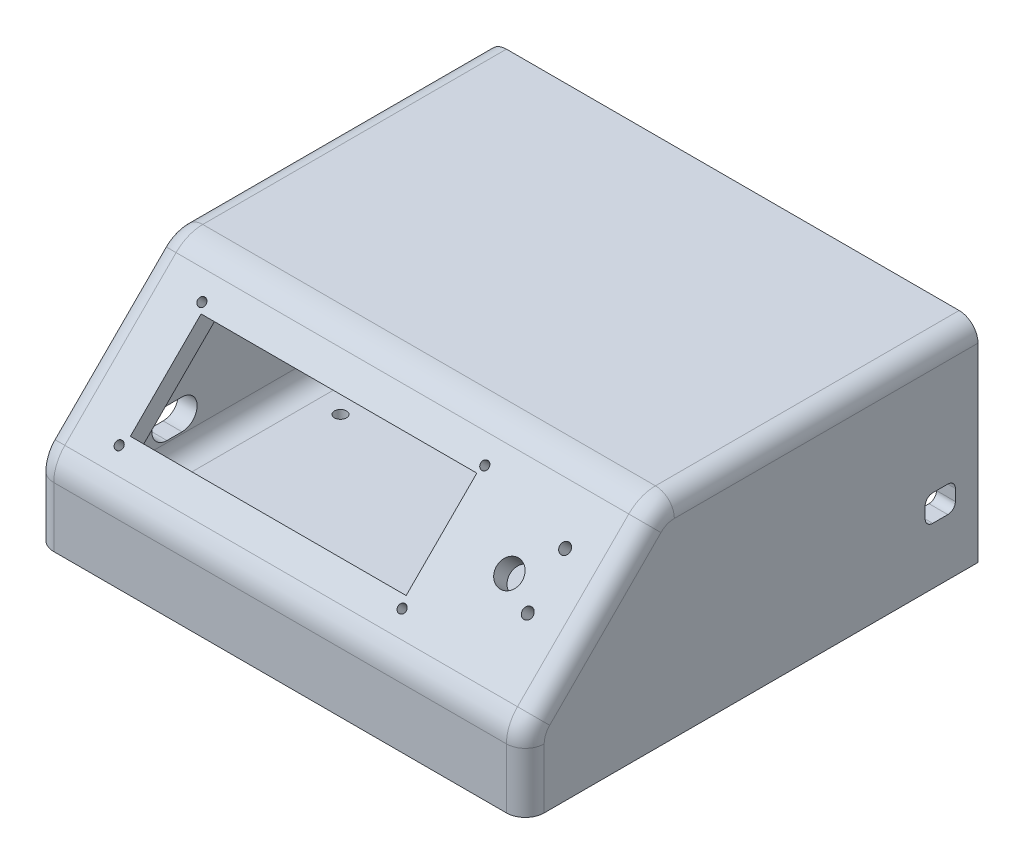
SolidWorks part; units mm, degrees
ref_plane "Front Plane" through (0, 0, 0) normal (0, 0, 1) x (1, 0, 0)
ref_plane "Top Plane" through (0, 0, 0) normal (0, 1, 0) x (1, 0, 0)
ref_plane "Right Plane" through (0, 0, 0) normal (1, 0, 0) x (0, 0, -1)
sketch "Sketch2" plane through (0, 0, 0) normal (1, 0, 0) x (0, 0, -1)
  line L0 (0, 0) -> (0, 20)
  line L1 (0, 20) -> (35.3553, 55.3553)
  line L2 (35.3553, 55.3553) -> (120, 55.3553)
  line L3 (120, 55.3553) -> (120, 0)
  line L4 (120, 0) -> (0, 0)
  dimension "D1" = 20
  dimension "D2" = 50
  dimension "D3" = 135
  dimension "D4" = 120
extrude "Boss-Extrude1" add sketch "Sketch2" along normal blind 130
shell "Shell1" thickness 5 removed face at (65, 27.6777, -120)
sketch "Sketch3" plane through (0, 10, 10) normal (0, 0.7071, 0.7071) x (1, 0, 0)
  line L0 (0, 64.1421) -> (0, 14.1421) construction
  line L1 (17, 52.3921) -> (90.1, 52.3921)
  line L2 (17, 52.3921) -> (17, 25.8921)
  line L3 (17, 25.8921) -> (90.1, 25.8921)
  line L4 (90.1, 52.3921) -> (90.1, 25.8921)
  circle A0 centre (108.1, 39.1421) radius 3.4
  point P6 (0, 39.1421)
  point P7 (17, 39.1421)
  point P11 (90.1, 39.1421)
  dimension "D3" = 6.8
  dimension "D1" = 73.1
  dimension "D2" = 26.5
  dimension "D4" = 18
  dimension "D5" = 17
extrude "Cut-Extrude1" cut sketch "Sketch3" against normal up to surface (5 mm away) up to face at (65, 34.1421, -21.2132)
fillet "Fillet1" radius 10 5 edges at (65, 20, 0) (65, 55.3553, -35.3553) (65, 50.3553, -37.4264) (65, 5, -5) (65, 17.9289, -5)
fillet "Fillet2" radius 5 10 edges at (0, 55.3553, -79.7487) (0, 54.5941, -35.6706) (0, 37.6777, -17.6777) (0, 19.6847, -0.7612) (130, 55.3553, -79.7487) (130, 54.5941, -35.6706) (130, 37.6777, -17.6777) (130, 19.6847, -0.7612) (0, 7.9289, 0) (130, 7.9289, 0)
sketch "Sketch4" plane through (130, 0, 0) normal (1, 0, 0) x (0, 0, -1)
  line L0 (5, 0) -> (120, 0) construction
  line L1 (108, 22) -> (112, 22)
  line L2 (106, 20) -> (106, 17)
  line L3 (108, 15) -> (112, 15)
  line L4 (114, 20) -> (114, 17)
  line L5 (120, 0) -> (120, 50.3553) construction
  arc A0 (106, 17) -> (108, 15) centre (108, 17) ccw
  arc A1 (112, 15) -> (114, 17) centre (112, 17) ccw
  arc A2 (112, 22) -> (114, 20) centre (112, 20) cw
  arc A3 (108, 22) -> (106, 20) centre (108, 20) ccw
  point P8 (114, 15)
  point P11 (114, 22)
  point P14 (106, 22)
  dimension "D3" = 2
  dimension "D1" = 8
  dimension "D2" = 7
  dimension "D4" = 15
  dimension "D5" = 6
extrude "Cut-Extrude2" cut sketch "Sketch4" against normal up to surface (5 mm away) up to face at (125, 27.4827, -48.7525)
fillet "Fillet3" radius 5 12 edges at (125, 7.7176, -8.1468) (125, 17.8922, -5.8816) (125, 34.1421, -21.2132) (125, 49.5941, -37.7417) (5, 7.7176, -8.1468) (5, 17.8922, -5.8816) (5, 34.1421, -21.2132) (5, 49.5941, -37.7417) (125, 5, -67.5) (125, 50.3553, -80.7843) (5, 5, -67.5) (5, 50.3553, -80.7843)
sketch "Sketch5" plane through (0, 10, 10) normal (0, 0.7071, 0.7071) x (1, 0, 0)
  line L0 (102.2, 33.1421) -> (114, 45.1421) construction
  line L1 (102.2, 45.1421) -> (114, 45.1421) construction
  line L2 (102.2, 45.1421) -> (102.2, 33.1421) construction
  line L3 (102.2, 33.1421) -> (114, 33.1421) construction
  line L4 (114, 45.1421) -> (114, 33.1421) construction
  line L6 (99.8, 55.0421) -> (118.6, 55.0421) construction
  line L7 (99.8, 55.0421) -> (99.8, 28.7421) construction
  line L8 (99.8, 28.7421) -> (118.6, 28.7421) construction
  line L9 (118.6, 55.0421) -> (118.6, 28.7421) construction
  circle A0 centre (108.1, 39.1421) radius 3.4 construction
  circle A1 centre (108.1, 39.1421) radius 3.4 construction
  circle A2 centre (116.3, 48.4421) radius 1.4
  circle A3 centre (116.3, 34.4421) radius 1.4
  point P8 (108.1, 39.1421)
  dimension "D7" = 2.8
  dimension "D1" = 12
  dimension "D2" = 11.8
  dimension "D3" = 2.4
  dimension "D4" = 18.8
  dimension "D5" = 26.3
  dimension "D6" = 4.4
  dimension "D8" = 14
  dimension "D9" = 5.7
  dimension "D10" = 16.5
extrude "Cut-Extrude3" cut sketch "Sketch5" against normal up to next
sketch "Sketch6" plane through (0, 10, 10) normal (0, 0.7071, 0.7071) x (1, 0, 0)
  line L0 (90.1, 52.3921) -> (17, 52.3921) construction
  line L1 (13.3, 57.3921) -> (93.8, 57.3921) construction
  line L2 (13.3, 57.3921) -> (13.3, 20.8921) construction
  line L3 (13.3, 20.8921) -> (93.8, 20.8921) construction
  line L4 (93.8, 57.3921) -> (93.8, 20.8921) construction
  line L5 (17, 52.3921) -> (17, 25.8921) construction
  circle A0 centre (15.8, 54.3921) radius 1.1
  circle A1 centre (90.8, 54.3921) radius 1.1
  circle A2 centre (90.8, 23.3921) radius 1.1
  circle A3 centre (15.8, 23.3921) radius 1.1
  point P16 (13.3, 39.1421)
  point P17 (17, 39.1421)
  point P19 (53.55, 57.3921)
  point P20 (53.55, 52.3921)
  dimension "D3" = 2.2
  dimension "D1" = 75
  dimension "D2" = 31
  dimension "D4" = 5
  dimension "D5" = 3.7
  dimension "D6" = 3
  dimension "D7" = 2.5
extrude "Cut-Extrude4" cut sketch "Sketch6" against normal up to next
sketch "Sketch7" plane through (0, 5, 0) normal (0, 1, 0) x (1, 0, 0)
  line L0 (109.5, 21.5) -> (113, 21.5) construction
  line L1 (113, 18) -> (13, 18) construction
  line L2 (113, 18) -> (113, 68) construction
  line L3 (113, 68) -> (13, 68) construction
  line L4 (13, 18) -> (13, 68) construction
  line L5 (109.5, 21.5) -> (109.5, 18) construction
  line L7 (16.5, 21.5) -> (13, 21.5) construction
  line L8 (16.5, 21.5) -> (16.5, 18) construction
  line L9 (109.5, 64.5) -> (109.5, 68) construction
  line L10 (10, 120) -> (10, 15) construction
  line L11 (10, 15) -> (120, 15) construction
  line L12 (120, 120) -> (10, 120) construction
  line L13 (111, 77) -> (51, 77) construction
  line L14 (111, 77) -> (111, 117) construction
  line L15 (111, 117) -> (51, 117) construction
  line L16 (51, 77) -> (51, 117) construction
  line L17 (109, 79) -> (109, 77) construction
  line L18 (109, 79) -> (111, 79) construction
  line L19 (53, 79) -> (51, 79) construction
  line L20 (109, 115) -> (109, 117) construction
  circle A0 centre (16.5, 21.5) radius 1.5
  circle A1 centre (16.5, 64.5) radius 1.5
  circle A2 centre (109.5, 21.5) radius 1.5
  circle A3 centre (109.5, 64.5) radius 1.5
  circle A4 centre (109, 79) radius 1.5
  circle A5 centre (53, 79) radius 1.5
  circle A6 centre (53, 115) radius 1.5
  circle A7 centre (109, 115) radius 1.5
  dimension "D1" = 3
  dimension "D12" = 2
  dimension "D2" = 43
  dimension "D3" = 93
  dimension "D4" = 100
  dimension "D5" = 50
  dimension "D6" = 3
  dimension "D7" = 3
  dimension "D8" = 40
  dimension "D9" = 60
  dimension "D10" = 2
  dimension "D11" = 3
  dimension "D13" = 2
extrude "Cut-Extrude5" cut sketch "Sketch7" against normal up to next
hole_wizard "CSK for M3 Countersunk Flat Head Screw2" positions "Sketch12" profile "Sketch13" countersink size "M3" standard "ISO"
sketch "Sketch12" plane through (0, 0, 0) normal (0, -1, 0) x (-1, 0, 0)
  point P0 (-109, 115)
  point P3 (-53, 115)
  point P6 (-53, 79)
  point P9 (-109, 79)
  point P12 (-16.5, 64.5)
  point P15 (-16.5, 21.5)
  point P18 (-109.5, 21.5)
  point P21 (-109.5, 64.5)
sketch "Sketch13" plane through (109, 0, -115) normal (1, 0, 0) x (0, 0, -1)
  line L0 (0, 0) -> (0, 8.9614)
  line L1 (0, 8.9614) -> (1.6, 8)
  line L2 (1.6, 8) -> (1.6, 1.55)
  line L3 (1.6, 1.55) -> (3.15, 0)
  line L5 (3.15, 0) -> (0, 0)
  line L6 (-1.6, 1.55) -> (-3.15, 0) construction
  line L10 (0, 8.9614) -> (-1.6, 8) construction
  line L11 (0, -6.35) -> (0, 107.95) construction
  dimension "Hole Dia." = 3.2
  dimension "Hole Depth" = 8
  dimension "Near C'Sink Dia." = 6.3
  dimension "Near C'Sink Angle" = 90
  dimension "Drill Angle" = 118
sketch "Sketch14" plane through (0, 0, 0) normal (-1, 0, 0) x (0, 0, 1)
  line L0 (-34, 14.5) -> (-30, 14.5) construction
  line L1 (-34, 18.5) -> (-30, 18.5)
  line L2 (-34, 10.5) -> (-30, 10.5)
  line L3 (-5, 0) -> (-120, 0) construction
  line L4 (-120, 0) -> (-120, 50.3553) construction
  line L5 (-19.9, 5) -> (-23.1, 5) construction
  line L6 (-19.9, 5) -> (-23.1, 5) construction
  arc A0 (-34, 18.5) -> (-34, 10.5) centre (-34, 14.5) ccw
  arc A1 (-30, 10.5) -> (-30, 18.5) centre (-30, 14.5) ccw
  point P2 (-32, 14.5)
  dimension "D1" = 4
  dimension "D2" = 4
  dimension "D3" = 14.5
  dimension "D4" = 86
extrude "Cut-Extrude6" cut sketch "Sketch14" against normal up to next
sketch "Sketch15" plane through (0, 0, -120) normal (0, 0, -1) x (-1, 0, 0)
  line L0 (-125, 55.3553) -> (-5, 55.3553) construction
  line L1 (-130, 0) -> (-130, 50.3553) construction
  line L2 (0, 0) -> (0, 50.3553) construction
  line L3 (-130, 0) -> (0, 0) construction
  circle A0 centre (-126, 51.3553) radius 1.2
  circle A1 centre (-126, 4) radius 1.2
  circle A2 centre (-4, 4) radius 1.2
  circle A3 centre (-4, 51.3553) radius 1.2
  dimension "D1" = 2.4
  dimension "D2" = 4
  dimension "D3" = 4
  dimension "D4" = 4
  dimension "D5" = 4
extrude "Cut-Extrude7" cut sketch "Sketch15" against normal blind 20
sketch "Sketch16" plane through (0, 0, -120) normal (0, 0, -1) x (-1, 0, 0)
  line L4 (0, 0) -> (0, 50.3553)
  line L5 (-5, 55.3553) -> (-125, 55.3553)
  line L6 (-130, 50.3553) -> (-130, 0)
  line L7 (-130, 0) -> (0, 0)
  line L8 (0, 0) -> (0, 50.3553)
  line L9 (-5, 55.3553) -> (-125, 55.3553)
  line L10 (-130, 50.3553) -> (-130, 0)
  line L11 (-130, 0) -> (0, 0)
  circle A0 centre (-126, 4) radius 1.2 construction
  circle A1 centre (-4, 4) radius 1.2 construction
  arc A2 (0, 50.3553) -> (-5, 55.3553) centre (-5, 50.3553) ccw
  arc A3 (-125, 55.3553) -> (-130, 50.3553) centre (-125, 50.3553) ccw
  arc A4 (0, 50.3553) -> (-5, 55.3553) centre (-5, 50.3553) ccw
  arc A5 (-125, 55.3553) -> (-130, 50.3553) centre (-125, 50.3553) ccw
  circle A6 centre (-4, 51.3553) radius 1.2 construction
  circle A7 centre (-126, 51.3553) radius 1.2 construction
  circle A8 centre (-126, 4) radius 1.2
  circle A9 centre (-4, 4) radius 1.2
  circle A10 centre (-4, 51.3553) radius 1.2
  circle A11 centre (-126, 51.3553) radius 1.2
  dimension "D1" = 0
extrude "Boss-Extrude2" add sketch "Sketch16" along normal blind 5 separate body
hole_wizard "CSK for M3 Countersunk Flat Head Screw3" positions "Sketch19" profile "Sketch20" countersink size "M3" standard "ISO"
sketch "Sketch19" plane through (0, 0, -125) normal (0, 0, -1) x (-1, 0, 0)
  point P0 (-126, 51.3553)
  point P3 (-126, 4)
  point P6 (-4, 51.3553)
  point P9 (-4, 4)
sketch "Sketch20" plane through (126, 51.3553, -125) normal (1, 0, 0) x (0, 1, 0)
  line L0 (0, 0) -> (0, 8.9614)
  line L1 (0, 8.9614) -> (1.6, 8)
  line L2 (1.6, 8) -> (1.6, 1.55)
  line L3 (1.6, 1.55) -> (3.15, 0)
  line L5 (3.15, 0) -> (0, 0)
  line L6 (-1.6, 1.55) -> (-3.15, 0) construction
  line L10 (0, 8.9614) -> (-1.6, 8) construction
  line L11 (0, -6.35) -> (0, 107.95) construction
  dimension "Hole Dia." = 3.2
  dimension "Hole Depth" = 8
  dimension "Near C'Sink Dia." = 6.3
  dimension "Near C'Sink Angle" = 90
  dimension "Drill Angle" = 118
delete or keep bodies "Body-Delete/Keep 1" type delete bodies bodies 112
